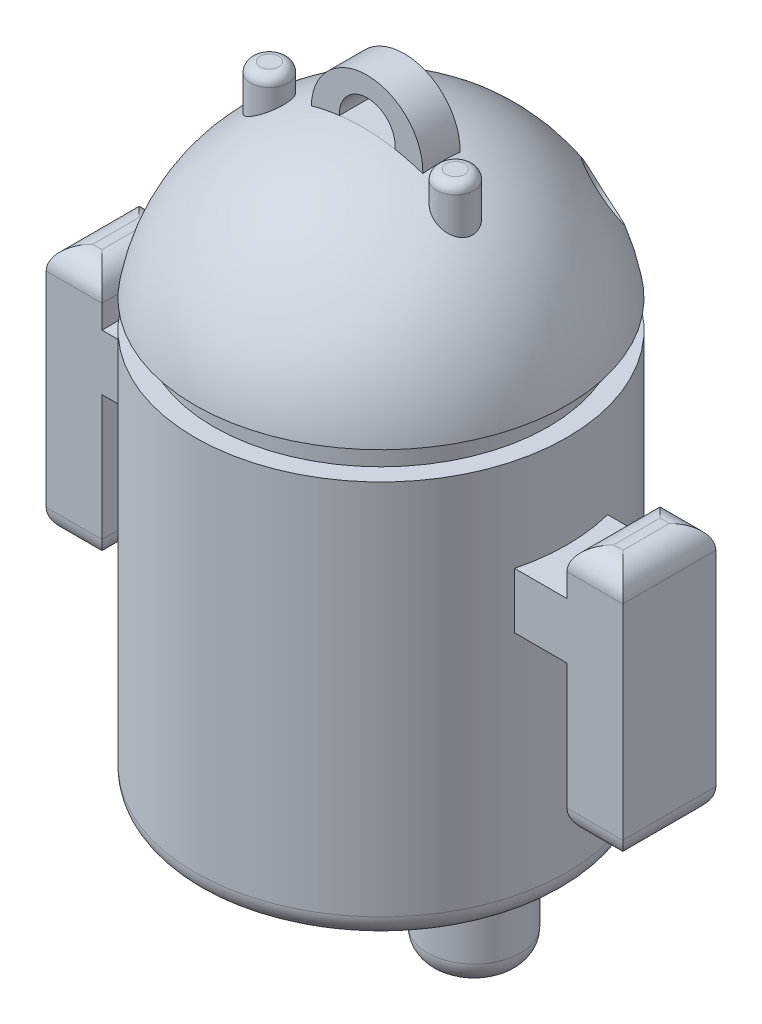
SolidWorks part; units mm, degrees
ref_plane "Alzado" through (0, 0, 0) normal (0, 0, 1) x (1, 0, 0)
ref_plane "Planta" through (0, 0, 0) normal (0, 1, 0) x (1, 0, 0)
ref_plane "Vista lateral" through (0, 0, 0) normal (1, 0, 0) x (0, 0, -1)
sketch "Croquis1" plane through (0, 0, 0) normal (0, 0, 1) x (1, 0, 0)
  line L8 (0, 63) -> (0, 0)
  line L9 (20, 43) -> (20, 0)
  line L10 (20, 0) -> (0, 0)
  line L11 (20, 43) -> (18, 43)
  line L12 (18, 43) -> (18, 46)
  line L13 (18, 46) -> (20, 46)
  arc A1 (0, 63) -> (20, 43) centre (0, 43) ccw construction
  arc A2 (0, 63) -> (20, 46) centre (0, 42.7353) cw
  point P9 (0, 0)
  dimension "D1" = 63
  dimension "D6" = 20
  dimension "D2" = 20
  dimension "D3" = 43
  dimension "D4" = 2
  dimension "D5" = 3
  dimension "D7" = 2
revolve "Revolución1" add sketch "Croquis1" angle 360 about L8
sketch "Croquis2" plane through (0, 0, 0) normal (0, 0, 1) x (1, 0, 0)
  line L0 (0, 81.4364) -> (0, -16.608) construction
  line L1 (-20, 46) -> (20, 46) construction
  circle A0 centre (-8, 52) radius 3
  circle A1 centre (8, 52) radius 3
  dimension "D1" = 8
  dimension "D3" = 6
  dimension "D2" = 6
extrude "Cortar-Extruir1" cut sketch "Croquis2" against normal through all
sketch "Croquis9" plane through (0, 0, 0) normal (0, 1, 0) x (1, 0, 0)
  line L0 (1.7714, 0) -> (-24.3358, 0) construction
  circle A0 centre (-10, -2) radius 2
  circle A1 centre (0, 0) radius 20 construction
  dimension "D1" = 4
  dimension "D2" = 10
  dimension "D3" = 2
extrude "Saliente-Extruir4" add sketch "Croquis9" along normal blind 64
sketch "Croquis12" plane through (0, 0, 0) normal (0, 1, 0) x (1, 0, 0)
  line L0 (22.7254, 0) -> (-24.9442, 0) construction
  line L1 (0, -10.3399) -> (0, 13.115) construction
  circle A0 centre (-10, 0) radius 5
  dimension "D1" = 10
  dimension "D2" = 0
  dimension "D3" = 10
extrude "Saliente-Extruir7" add sketch "Croquis12" against normal blind 10 contours A0
sketch "Croquis17" plane through (0, 0, 0) normal (0, 0, 1) x (1, 0, 0)
  line L0 (28.6875, 30) -> (-34.6279, 30) construction
  line L2 (-5, 27) -> (-25, 27)
  line L4 (-25, 33) -> (-5, 33)
  line L6 (-25, 33) -> (-25, 38)
  line L7 (-25, 38) -> (-31, 38)
  line L8 (-31, 38) -> (-31, 11)
  line L9 (-31, 11) -> (-25, 11)
  line L10 (-25, 11) -> (-25, 27)
  line L11 (-25, 33) -> (-25, 38)
  line L12 (-5, 27) -> (-5, 33)
  line L15 (-20, 43) -> (-20, 0) construction
  dimension "D1" = 6
  dimension "D2" = 27
  dimension "D3" = 16
  dimension "D4" = 20
  dimension "D5" = 6
  dimension "D6" = 20
  dimension "D7" = 5
  dimension "D8" = 5
  dimension "D9" = 30
extrude "Saliente-Extruir8" add sketch "Croquis17" along normal mid plane 10 contours L0 L12 L4 L6 L7 L8 | L12 L0 L8 L9 L10 L2 region at (-5.322, 28.5, 0) region at (-20.7778, 32.6111, 0)
mirror "Simetría4" about plane through (0, 0, 0) normal (1, 0, 0) of "Saliente-Extruir7", "Saliente-Extruir8", "Saliente-Extruir4"
sketch "Croquis18" plane through (0, 0, 0) normal (0, 0, 1) x (1, 0, 0)
  line L0 (20, 43) -> (-20, 43) construction
  line L1 (-8, 61.2463) -> (-8, 64) construction
  line L2 (25.3604, 62) -> (-30.173, 62) construction
  circle A0 centre (0.5, 62) radius 6
  circle A1 centre (0.5, 62) radius 3.5 construction
  dimension "D1" = 19
  dimension "D2" = 12
  dimension "D4" = 62
  dimension "D5" = 2.5
  dimension "D3" = 8.5
extrude "Saliente-Extruir10" add sketch "Croquis18" along normal mid plane 4
sketch "Croquis20" plane through (0, 0, -2) normal (0, 0, -1) x (-1, 0, 0)
  circle A0 centre (-0.5232, 62.8943) radius 3 construction
  arc A1 (5.4984, 62.137) -> (-6.4975, 61.8256) centre (0, 42.7353) ccw construction
  arc A2 (-3.5081, 62.5936) -> (2.4733, 62.7488) centre (0, 42.7353) cw
  arc A3 (-3.5081, 62.5936) -> (2.4733, 62.7488) centre (-0.5232, 62.8943) cw
  arc A4 (5.4984, 62.137) -> (-6.4975, 61.8256) centre (-0.5, 62) ccw construction
  dimension "D1" = 3
  dimension "D2" = 0.8946
  dimension "D3" = 42.7353
extrude "Cortar-Extruir7" cut sketch "Croquis20" against normal blind 4
fillet "Redondeo7" radius 1 2 edges at (-10, 64, 4) (10, 64, 4)
fillet "Redondeo8" radius 2.5 2 edges at (-10, -10, 5) (10, -10, 5)
fillet "Redondeo9" radius 2.5 8 edges at (-31, 11, 0) (-28, 11, 5) (-25, 11, 0) (-28, 11, -5) (25, 11, 0) (28, 11, 5) (31, 11, 0) (28, 11, -5)
fillet "Redondeo10" radius 2.5 8 edges at (-25, 38, 0) (-28, 38, 5) (-31, 38, 0) (-28, 38, -5) (31, 38, 0) (28, 38, 5) (25, 38, 0) (28, 38, -5)
fillet "Redondeo13" radius 2.5 1 edges at (0, 0, 20) type face fillet first side face at (19.6825, 30, 0) second side face at (10, 0, 5)
